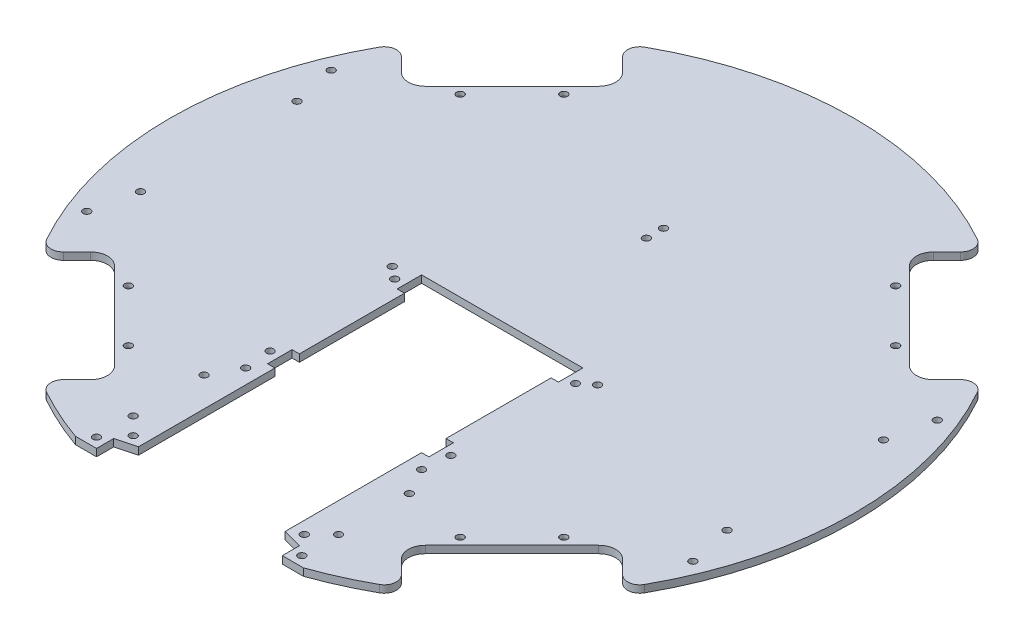
SolidWorks part; units mm, degrees
material "1060 Alloy"
ref_plane "Front Plane" through (0, 0, 0) normal (0, 0, 1) x (1, 0, 0)
ref_plane "Top Plane" through (0, 0, 0) normal (0, 1, 0) x (1, 0, 0)
ref_plane "Right Plane" through (0, 0, 0) normal (1, 0, 0) x (0, 0, -1)
sketch "Sketch1" plane through (0, 0, 0) normal (0, 1, 0) x (1, 0, 0)
  circle A0 centre (0, 0) radius 140
  dimension "D1" = 280
extrude "Boss-Extrude1" add sketch "Sketch1" along normal blind 3
sketch "Sketch7" plane through (0, 3, 0) normal (0, 1, 0) x (1, 0, 0)
  line L0 (-99.0303, -63.6043) -> (-63.6043, -99.0303)
  line L1 (-108.8591, -63.6043) -> (-121.6224, -76.3675)
  line L2 (-63.6043, -108.8591) -> (-76.3675, -121.6224)
  line L3 (-121.6224, -76.3675) -> (-76.3675, -121.6224)
  line L4 (0, 0) -> (-98.9949, -98.9949) construction
  line L7 (0, 0) -> (0, 130) construction
  circle A0 centre (0, 0) radius 140 construction
  arc A1 (-108.8591, -63.6043) -> (-99.0303, -63.6043) centre (-103.9447, -68.5186) cw
  arc A2 (-63.6043, -99.0303) -> (-63.6043, -108.8591) centre (-68.5186, -103.9447) cw
  dimension "D4" = 6.95
  dimension "D1" = 115
  dimension "D2" = 64
  dimension "D3" = 135
extrude "Cut-Extrude4" cut sketch "Sketch7" against normal up to next
sketch "Sketch9" plane through (0, 3, 0) normal (0, 1, 0) x (1, 0, 0)
  line L1 (-63.6043, -99.0303) -> (-99.0303, -63.6043) construction
  line L4 (-108.8591, -63.6043) -> (-119.0017, -73.7469) construction
  circle A0 centre (-89.0955, -67.8823) radius 1.5
  circle A1 centre (-67.8823, -89.0955) radius 1.5
  dimension "D4" = 3
  dimension "D1" = 4
  dimension "D2" = 30
  dimension "D3" = 17
  dimension "D5" = 4
extrude "Cut-Extrude6" cut sketch "Sketch9" against normal up to next
fillet "Fillet1" radius 5 2 edges at (-73.7469, 1.5, 119.0017) (-119.0017, 1.5, 73.7469)
pattern_circular "CirPattern1" count 4 over 360 about axis through (0, 3, 0) along (0, 1, 0) of "Cut-Extrude4", "Fillet1", "Cut-Extrude6"
sketch "Sketch2" plane through (0, 3, 0) normal (0, 1, 0) x (1, 0, 0)
  line L0 (-46.6476, -132) -> (-38, -132)
  line L1 (-30, -122.8564) -> (-30, -67)
  line L2 (-33, -4) -> (33, -4)
  line L3 (30, -67) -> (30, -122.8564)
  line L4 (38, -132) -> (46.6476, -132)
  line L5 (46.6476, -132) -> (46.6476, -140)
  line L6 (46.6476, -140) -> (-46.6476, -140)
  line L7 (-46.6476, -140) -> (-46.6476, -132)
  line L8 (-33, -57) -> (-33, -67)
  line L9 (-33, -67) -> (-30, -67)
  line L10 (33, -57) -> (33, -67)
  line L11 (33, -67) -> (30, -67)
  line L12 (-33, -57) -> (-30, -57)
  line L13 (-30, -57) -> (-30, -14)
  line L14 (-30, -14) -> (-33, -14)
  line L15 (-33, -14) -> (-33, -4)
  line L16 (33, -4) -> (33, -14)
  line L17 (33, -14) -> (30, -14)
  line L18 (30, -14) -> (30, -57)
  line L19 (30, -57) -> (33, -57)
  line L20 (-38, -132) -> (-38, -125)
  line L21 (-38, -125) -> (-30, -122.8564)
  line L22 (38, -132) -> (38, -125)
  line L23 (38, -125) -> (30, -122.8564)
  circle A0 centre (0, 0) radius 140 construction
  dimension "D8" = 3
  dimension "D5" = 63
  dimension "D6" = 66
  dimension "D1" = 8
  dimension "D2" = 65
  dimension "D3" = 60
  dimension "D4" = 16.6476
  dimension "D7" = 10
  dimension "D9" = 76
  dimension "D10" = 7
  dimension "D11" = 105
extrude "Cut-Extrude1" cut sketch "Sketch2" against normal up to next
fillet "Fillet3" radius 1.5 8 edges at (67.8823, 0, 90.5955) (89.0955, 0, 69.3823) (89.0955, 0, -66.3823) (67.8823, 0, -87.5955) (-67.8823, 0, -87.5955) (-89.0955, 0, -66.3823) (-67.8823, 0, 90.5955) (-89.0955, 0, 69.3823)
sketch "Sketch10" plane through (0, 3, 0) normal (0, 1, 0) x (1, 0, 0)
  line L0 (-33, -57) -> (-33, -67) construction
  line L1 (33, -67) -> (33, -57) construction
  line L2 (-33, -67) -> (-30, -67) construction
  line L4 (-30, -14) -> (-33, -14) construction
  line L5 (33, -4) -> (-33, -4) construction
  circle A0 centre (-37, -62) radius 1.5
  circle A1 centre (37, -62) radius 1.5
  circle A2 centre (-37, -11) radius 1.5
  circle A3 centre (37, -11) radius 1.5
  circle A4 centre (-42, -7) radius 1.5
  circle A5 centre (42, -7) radius 1.5
  point P17 (-31.5, -14)
  dimension "D3" = 3
  dimension "D1" = 4
  dimension "D2" = 4
  dimension "D4" = 5
  dimension "D5" = 3
  dimension "D6" = 3
  dimension "D7" = 5
  dimension "D8" = 5
extrude "Cut-Extrude7" cut sketch "Sketch10" against normal up to next
sketch "Sketch13" plane through (0, 3, 0) normal (0, 1, 0) x (1, 0, 0)
  line L0 (-38, -132) -> (-46.6476, -132) construction
  line L1 (-38, -132) -> (-46.6476, -132) construction
  circle A0 centre (-42, -84) radius 1.5
  circle A1 centre (-42, -113) radius 1.5
  circle A2 centre (42, -113) radius 1.5
  circle A3 centre (42, -84) radius 1.5
  dimension "D1" = 3
  dimension "D2" = 19
  dimension "D3" = 48
  dimension "D4" = 42
  dimension "D5" = 42
extrude "Cut-Extrude9" cut sketch "Sketch13" against normal up to next
sketch "Sketch16" plane through (0, 3, 0) normal (0, 1, 0) x (1, 0, 0)
  circle A0 centre (0, 62) radius 1.5
  circle A4 centre (0, 55) radius 1.5
  dimension "D2" = 3
  dimension "D5" = 3
  dimension "D1" = 62
  dimension "D7" = 55
extrude "Cut-Extrude12" cut sketch "Sketch16" against normal up to next
sketch "Sketch17" plane through (0, 3, 0) normal (0, 1, 0) x (1, 0, 0)
  circle A0 centre (-124, 50) radius 1.5
  circle A1 centre (-124, -50) radius 1.5
  circle A2 centre (124, 50) radius 1.5
  circle A3 centre (124, -50) radius 1.5
  dimension "D1" = 3
  dimension "D2" = 50
  dimension "D3" = 50
  dimension "D4" = 124
  dimension "D5" = 124
extrude "Cut-Extrude13" cut sketch "Sketch17" against normal up to next
sketch "Sketch18" plane through (0, 3, 0) normal (0, 1, 0) x (1, 0, 0)
  line L1 (-27, -4) -> (27, -4)
  line L2 (-27, -4) -> (-27, 46)
  line L3 (-27, 46) -> (27, 46)
  line L4 (27, -4) -> (27, 46)
  line L5 (33, -4) -> (-33, -4) construction
  dimension "D1" = 50
  dimension "D2" = 54
  dimension "D3" = 27
extrude "Cut-Extrude14" [suppressed] cut sketch "Sketch18" against normal blind 0.8
sketch "Sketch19" plane through (0, 3, 0) normal (0, 1, 0) x (1, 0, 0)
  line L0 (-38, -125) -> (-38, -132) construction
  line L1 (-38, -132) -> (-46.6476, -132) construction
  line L2 (38, -132) -> (38, -125) construction
  circle A0 centre (-42, -128) radius 1.5
  circle A1 centre (42, -128) radius 1.5
  dimension "D4" = 3
  dimension "D1" = 4
  dimension "D2" = 4
  dimension "D3" = 4
extrude "Cut-Extrude15" cut sketch "Sketch19" against normal up to next
sketch "Sketch20" [suppressed] plane through (0, 3, 0) normal (0, 1, 0) x (1, 0, 0)
  line L0 (27, 46) -> (-27, 46) construction
  line L1 (-6, 46) -> (6, 46)
  line L2 (-6, 46) -> (-6, 52)
  line L3 (-6, 52) -> (6, 52)
  line L4 (6, 46) -> (6, 52)
  circle A0 centre (0, 55) radius 1.5 construction
  dimension "D1" = 12
  dimension "D2" = 6
  dimension "D3" = 3
extrude "Cut-Extrude16" [suppressed] cut sketch "Sketch20" against normal up to surface (0.8 mm away) up to face at (42, 3, 129.5)
fillet "Fillet4" [suppressed] radius 1.5
sketch "Sketch21" plane through (0, 3, 0) normal (0, 1, 0) x (1, 0, 0)
  circle A0 centre (-35, -120) radius 1.5
  circle A1 centre (-36, -73) radius 1.5
  circle A2 centre (35, -120) radius 1.5
  circle A3 centre (36, -73) radius 1.5
  circle A4 centre (-42, -128) radius 1.5 construction
  circle A5 centre (42, -128) radius 1.5 construction
  dimension "D1" = 7
  dimension "D3" = 3
  dimension "D2" = 8
  dimension "D4" = 47
  dimension "D5" = 1
  dimension "D6" = 1
  dimension "D7" = 7
extrude "Cut-Extrude17" cut sketch "Sketch21" against normal up to next
sketch "Sketch22" plane through (0, 3, 0) normal (0, 1, 0) x (1, 0, 0)
  circle A0 centre (120, 32) radius 1.5
  circle A1 centre (120, -32) radius 1.5
  circle A2 centre (-120, 32) radius 1.5
  circle A3 centre (-120, -32) radius 1.5
  dimension "D1" = 3
  dimension "D2" = 120
  dimension "D3" = 32
  dimension "D4" = 32
  dimension "D5" = 120
extrude "Cut-Extrude18" cut sketch "Sketch22" against normal up to next
